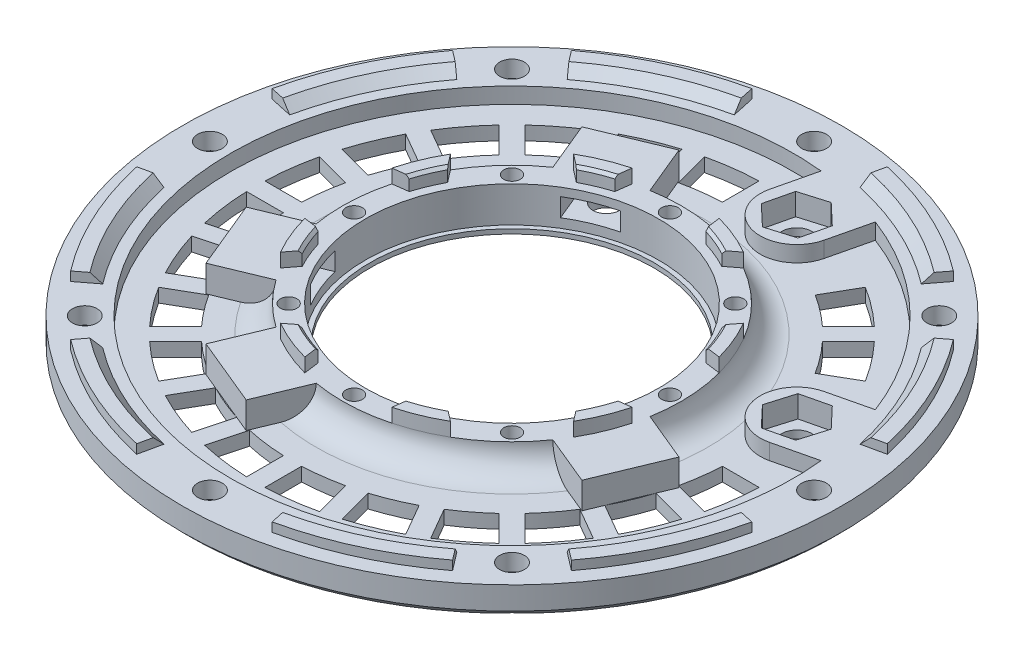
SolidWorks part; units mm, degrees
ref_plane "Front Plane" through (0, 0, 0) normal (0, 0, 1) x (1, 0, 0)
ref_plane "Top Plane" through (0, 0, 0) normal (0, 1, 0) x (1, 0, 0)
ref_plane "Right Plane" through (0, 0, 0) normal (1, 0, 0) x (0, 0, -1)
sketch "Sketch1" plane through (0, 0, 0) normal (0, 1, 0) x (1, 0, 0)
  circle A0 centre (0, 0) radius 16.025
  circle A1 centre (0, 0) radius 36
  dimension "D1" = 32.05
  dimension "D2" = 72
extrude "Boss-Extrude1" add sketch "Sketch1" along normal blind 1
sketch "Sketch2" plane through (0, 0, 0) normal (0, -1, 0) x (1, 0, 0)
  circle A0 centre (0, 0) radius 17.25 construction
  circle A1 centre (0, 0) radius 18.5 construction
  circle A2 centre (0, 0) radius 18.5
  circle A3 centre (0, 0) radius 16.025 construction
  circle A4 centre (0, 0) radius 16.025
  arc A5 (-1.2, 18.461) -> (-4.705, 17.8917) centre (0, 0) ccw construction
  point P3 (0, -17.25)
extrude "Boss-Extrude2" add sketch "Sketch2" against normal offset from surface (3.9 mm away) 3.9 up to face at (0, 0, 36)
fillet "Fillet1" radius 2.9 1 edges at (0, 1, 18.5)
sketch "Sketch4" plane through (0, 0, 0) normal (0, 1, 0) x (1, 0, 0)
  circle A0 centre (0, 0) radius 15.525
  circle A1 centre (0, 0) radius 36
  circle A2 centre (0, 0) radius 36
  circle A3 centre (0, 0) radius 16.025 construction
  dimension "D2" = 0.5
  dimension "D1" = 0
extrude "Boss-Extrude3" add sketch "Sketch4" against normal blind 0.5
sketch "Sketch5" plane through (0, 1, 0) normal (0, 1, 0) x (1, 0, 0)
  line L0 (27.99, -0.75) -> (19.9859, -0.75) construction
  line L1 (19.9859, 0.75) -> (27.99, 0.75) construction
  line L2 (27.99, -0.75) -> (19.9859, -0.75) construction
  line L3 (19.9859, 0.75) -> (27.99, 0.75) construction
  line L4 (0, 0) -> (36, 0) construction
  line L5 (0, 0) -> (34.7733, 9.3175) construction
  line L6 (34.7733, 9.3175) -> (36, 0) construction
  line L7 (0, 0) -> (35.3867, 4.6587) construction
  line L8 (27.99, 1) -> (23.9792, 1)
  line L9 (27.295, 6.2784) -> (23.4209, 5.2403)
  line L10 (27.99, -1) -> (23.9792, -1)
  line L11 (27.295, -6.2784) -> (23.4209, -5.2403)
  line L12 (26.7774, -8.2103) -> (22.9033, -7.1722)
  line L13 (24.74, -13.129) -> (21.2666, -11.1236)
  line L14 (23.74, -14.861) -> (20.2666, -12.8556)
  line L15 (20.499, -19.0848) -> (17.6629, -16.2487)
  line L16 (19.0848, -20.499) -> (16.2487, -17.6629)
  line L17 (14.861, -23.74) -> (12.8556, -20.2666)
  line L18 (13.129, -24.74) -> (11.1236, -21.2666)
  line L19 (8.2103, -26.7774) -> (7.1722, -22.9033)
  line L20 (6.2784, -27.295) -> (5.2403, -23.4209)
  line L21 (1, -27.99) -> (1, -23.9792)
  line L22 (-1, -27.99) -> (-1, -23.9792)
  line L23 (-6.2784, -27.295) -> (-5.2403, -23.4209)
  line L24 (-8.2103, -26.7774) -> (-7.1722, -22.9033)
  line L25 (-13.129, -24.74) -> (-11.1236, -21.2666)
  line L26 (-14.861, -23.74) -> (-12.8556, -20.2666)
  line L27 (-19.0848, -20.499) -> (-16.2487, -17.6629)
  line L28 (-20.499, -19.0848) -> (-17.6629, -16.2487)
  line L29 (-23.74, -14.861) -> (-20.2666, -12.8556)
  line L30 (-24.74, -13.129) -> (-21.2666, -11.1236)
  line L31 (-26.7774, -8.2103) -> (-22.9033, -7.1722)
  line L32 (-27.295, -6.2784) -> (-23.4209, -5.2403)
  line L33 (-27.99, -1) -> (-23.9792, -1)
  line L34 (-27.99, 1) -> (-23.9792, 1)
  line L35 (-27.295, 6.2784) -> (-23.4209, 5.2403)
  line L36 (-26.7774, 8.2103) -> (-22.9033, 7.1722)
  line L37 (-24.74, 13.129) -> (-21.2666, 11.1236)
  line L38 (-23.74, 14.861) -> (-20.2666, 12.8556)
  line L39 (-20.499, 19.0848) -> (-17.6629, 16.2487)
  line L40 (-19.0848, 20.499) -> (-16.2487, 17.6629)
  line L41 (-14.861, 23.74) -> (-12.8556, 20.2666)
  line L42 (-13.129, 24.74) -> (-11.1236, 21.2666)
  line L43 (-8.2103, 26.7774) -> (-7.1722, 22.9033)
  line L44 (-6.2784, 27.295) -> (-5.2403, 23.4209)
  line L45 (-1, 27.99) -> (-1, 23.9792)
  line L46 (1, 27.99) -> (1, 23.9792)
  line L47 (6.2784, 27.295) -> (5.2403, 23.4209)
  line L48 (8.2103, 26.7774) -> (7.1722, 22.9033)
  line L49 (13.129, 24.74) -> (11.1236, 21.2666)
  line L50 (14.861, 23.74) -> (12.8556, 20.2666)
  line L51 (19.0848, 20.499) -> (16.2487, 17.6629)
  line L52 (20.499, 19.0848) -> (17.6629, 16.2487)
  line L53 (23.74, 14.861) -> (20.2666, 12.8556)
  line L54 (24.74, 13.129) -> (21.2666, 11.1236)
  line L55 (26.7774, 8.2103) -> (22.9033, 7.1722)
  line L56 (0, 0) -> (23.9792, 1) construction
  circle A0 centre (0, 0) radius 24 construction
  circle A2 centre (0, 0) radius 36 construction
  arc A3 (23.9792, 1) -> (23.4209, 5.2403) centre (0, 0) ccw
  arc A4 (27.99, 1) -> (27.295, 6.2784) centre (0, 0) ccw
  arc A5 (27.295, -6.2784) -> (27.99, -1) centre (0, 0) ccw
  arc A6 (23.4209, -5.2403) -> (23.9792, -1) centre (0, 0) ccw
  arc A7 (24.74, -13.129) -> (26.7774, -8.2103) centre (0, 0) ccw
  arc A8 (21.2666, -11.1236) -> (22.9033, -7.1722) centre (0, 0) ccw
  arc A9 (20.499, -19.0848) -> (23.74, -14.861) centre (0, 0) ccw
  arc A10 (17.6629, -16.2487) -> (20.2666, -12.8556) centre (0, 0) ccw
  arc A11 (14.861, -23.74) -> (19.0848, -20.499) centre (0, 0) ccw
  arc A12 (12.8556, -20.2666) -> (16.2487, -17.6629) centre (0, 0) ccw
  arc A13 (8.2103, -26.7774) -> (13.129, -24.74) centre (0, 0) ccw
  arc A14 (7.1722, -22.9033) -> (11.1236, -21.2666) centre (0, 0) ccw
  arc A15 (1, -27.99) -> (6.2784, -27.295) centre (0, 0) ccw
  arc A16 (1, -23.9792) -> (5.2403, -23.4209) centre (0, 0) ccw
  arc A17 (-6.2784, -27.295) -> (-1, -27.99) centre (0, 0) ccw
  arc A18 (-5.2403, -23.4209) -> (-1, -23.9792) centre (0, 0) ccw
  arc A19 (-13.129, -24.74) -> (-8.2103, -26.7774) centre (0, 0) ccw
  arc A20 (-11.1236, -21.2666) -> (-7.1722, -22.9033) centre (0, 0) ccw
  arc A21 (-19.0848, -20.499) -> (-14.861, -23.74) centre (0, 0) ccw
  arc A22 (-16.2487, -17.6629) -> (-12.8556, -20.2666) centre (0, 0) ccw
  arc A23 (-23.74, -14.861) -> (-20.499, -19.0848) centre (0, 0) ccw
  arc A24 (-20.2666, -12.8556) -> (-17.6629, -16.2487) centre (0, 0) ccw
  arc A25 (-26.7774, -8.2103) -> (-24.74, -13.129) centre (0, 0) ccw
  arc A26 (-22.9033, -7.1722) -> (-21.2666, -11.1236) centre (0, 0) ccw
  arc A27 (-27.99, -1) -> (-27.295, -6.2784) centre (0, 0) ccw
  arc A28 (-23.9792, -1) -> (-23.4209, -5.2403) centre (0, 0) ccw
  arc A29 (-27.295, 6.2784) -> (-27.99, 1) centre (0, 0) ccw
  arc A30 (-23.4209, 5.2403) -> (-23.9792, 1) centre (0, 0) ccw
  arc A31 (-24.74, 13.129) -> (-26.7774, 8.2103) centre (0, 0) ccw
  arc A32 (-21.2666, 11.1236) -> (-22.9033, 7.1722) centre (0, 0) ccw
  arc A33 (-20.499, 19.0848) -> (-23.74, 14.861) centre (0, 0) ccw
  arc A34 (-17.6629, 16.2487) -> (-20.2666, 12.8556) centre (0, 0) ccw
  arc A35 (-14.861, 23.74) -> (-19.0848, 20.499) centre (0, 0) ccw
  arc A36 (-12.8556, 20.2666) -> (-16.2487, 17.6629) centre (0, 0) ccw
  arc A37 (-8.2103, 26.7774) -> (-13.129, 24.74) centre (0, 0) ccw
  arc A38 (-7.1722, 22.9033) -> (-11.1236, 21.2666) centre (0, 0) ccw
  arc A39 (-1, 27.99) -> (-6.2784, 27.295) centre (0, 0) ccw
  arc A40 (-1, 23.9792) -> (-5.2403, 23.4209) centre (0, 0) ccw
  arc A41 (6.2784, 27.295) -> (1, 27.99) centre (0, 0) ccw
  arc A42 (5.2403, 23.4209) -> (1, 23.9792) centre (0, 0) ccw
  arc A43 (13.129, 24.74) -> (8.2103, 26.7774) centre (0, 0) ccw
  arc A44 (11.1236, 21.2666) -> (7.1722, 22.9033) centre (0, 0) ccw
  arc A45 (19.0848, 20.499) -> (14.861, 23.74) centre (0, 0) ccw
  arc A46 (16.2487, 17.6629) -> (12.8556, 20.2666) centre (0, 0) ccw
  arc A47 (23.74, 14.861) -> (20.499, 19.0848) centre (0, 0) ccw
  arc A48 (20.2666, 12.8556) -> (17.6629, 16.2487) centre (0, 0) ccw
  arc A49 (26.7774, 8.2103) -> (24.74, 13.129) centre (0, 0) ccw
  arc A50 (22.9033, 7.1722) -> (21.2666, 11.1236) centre (0, 0) ccw
  dimension "D1" = 15
  dimension "D2" = 1
  dimension "D4" = 24
  dimension "D3" = 24
extrude "Cut-Extrude1" cut sketch "Sketch5" against normal through all both and the other way through all
sketch "Sketch7" plane through (0, 3.9, 0) normal (0, 1, 0) x (1, 0, 0)
  line L0 (0, 0) -> (0, 17.25) construction
  circle A0 centre (0, 17.25) radius 0.9
  circle A1 centre (12.1976, 12.1976) radius 0.9
  circle A2 centre (17.25, 0) radius 0.9
  circle A3 centre (12.1976, -12.1976) radius 0.9
  circle A4 centre (0, -17.25) radius 0.9
  circle A5 centre (-12.1976, -12.1976) radius 0.9
  circle A6 centre (-17.25, 0) radius 0.9
  circle A7 centre (-12.1976, 12.1976) radius 0.9
  point P21 (0, 0)
  dimension "D1" = 1.8
  dimension "D2" = 8
extrude "Cut-Extrude2" cut sketch "Sketch7" against normal through all
sketch "Sketch8" plane through (0, 1, 0) normal (0, 1, 0) x (1, 0, 0)
  arc A0 (-30.7407, -0.7544) -> (-30.0499, -6.5245) centre (0, 0) ccw construction
  arc A1 (-30.7407, -0.7544) -> (-30.0499, -6.5245) centre (0, 0) ccw construction
  arc A2 (-30.0499, 6.5245) -> (-30.7407, 0.7544) centre (0, 0) ccw construction
  arc A3 (-30.0499, 6.5245) -> (-30.7407, 0.7544) centre (0, 0) ccw construction
  circle A5 centre (0, 0) radius 30.75
  circle A6 centre (0, 0) radius 36 construction
  circle A7 centre (0, 0) radius 36
extrude "Boss-Extrude4" add sketch "Sketch8" along normal blind 1.7378
sketch "Sketch9" plane through (0, 2.7378, 0) normal (0, 1, 0) x (1, 0, 0)
  line L0 (0, 0) -> (-30.0499, 6.5245) construction
  line L1 (0, 0) -> (-30.0499, -6.5245) construction
  line L2 (-30.0499, 6.5245) -> (-30.0499, -6.5245) construction
  line L3 (-27.3707, 21.0023) -> (-23.9989, 18.415) construction
  line L4 (0, 0) -> (0, 36) construction
  line L5 (0, 0) -> (-25.4558, 25.4558) construction
  line L6 (-24.3956, 18.7194) -> (0, 0) construction
  line L7 (-24.3956, 18.7194) -> (-28.5607, 21.9154) construction
  line L8 (-30.0499, 6.5245) -> (-35.1803, 7.6384) construction
  line L9 (-27.3521, 20.862) -> (-25.3687, 19.3401)
  line L10 (-31.2086, 14.47) -> (0, 0) construction
  line L11 (-33.5954, 7.3966) -> (-31.1523, 6.8662)
  line L12 (-7.3966, 33.5954) -> (-6.8662, 31.1523)
  line L13 (-20.862, 27.3521) -> (-19.3401, 25.3687)
  arc A0 (-30.0499, 6.5245) -> (-24.3956, 18.7194) centre (0, 0) cw construction
  arc A1 (-35.1803, 7.6384) -> (-28.5607, 21.9154) centre (0, 0) cw construction
  circle A2 centre (0, 0) radius 36 construction
  circle A3 centre (0, 0) radius 30.75 construction
  arc A4 (-27.2914, 20.9414) -> (-33.6168, 7.2989) centre (0, 0) ccw construction
  arc A5 (-31.1523, 6.8662) -> (-25.3687, 19.3401) centre (0, 0) cw
  arc A6 (-33.5954, 7.3966) -> (-27.3521, 20.862) centre (0, 0) cw
  circle A7 centre (0, 0) radius 36 construction
  arc A8 (-6.8662, 31.1523) -> (-19.3401, 25.3687) centre (0, 0) ccw
  arc A9 (-7.3966, 33.5954) -> (-20.862, 27.3521) centre (0, 0) ccw
  dimension "D2" = 0.1
  dimension "D3" = 45
  dimension "D4" = 0.1
  dimension "D1" = 2.5
extrude "Boss-Extrude5" add sketch "Sketch9" along normal blind 1
ref_axis "Axis1" through (0, -0.72, 0) along (0, 1, 0)
pattern_circular "CirPattern1" count 4 over 360 about axis through (0, -0.72, 0) along (0, 1, 0) of "Boss-Extrude5"
chamfer "Chamfer1" distance 1 angle 45 8 edges at (-28.9406, 3.7378, -13.4184) (-13.4184, 3.7378, -28.9406) (13.4184, 3.7378, -28.9406) (28.9406, 3.7378, -13.4184) (28.9406, 3.7378, 13.4184) (13.4184, 3.7378, 28.9406) (-13.4184, 3.7378, 28.9406) (-28.9406, 3.7378, 13.4184)
sketch "Sketch10" plane through (0, 2.7378, 0) normal (0, 1, 0) x (1, 0, 0)
  line L0 (0, 0) -> (0, 36) construction
  circle A0 centre (0, 0) radius 36 construction
  circle A1 centre (0, 33) radius 1.1 construction
  circle A2 centre (0, 33) radius 1.1
  circle A3 centre (23.3345, 23.3345) radius 1.1
  circle A4 centre (33, 0) radius 1.1
  circle A5 centre (23.3345, -23.3345) radius 1.1
  circle A6 centre (0, -33) radius 1.1
  circle A7 centre (-23.3345, -23.3345) radius 1.1
  circle A8 centre (-33, 0) radius 1.1
  circle A9 centre (-23.3345, 23.3345) radius 1.1
  point P26 (0, 0)
  dimension "D1" = 8
extrude "Cut-Extrude3" cut sketch "Sketch10" against normal through all both and the other way through all
chamfer "Chamfer2" distance 0.75 angle 45 1 edges at (0, -0.5, 36)
hole_wizard "CSK for M2.5 Flat Head Machine Screw1" positions "Sketch11" profile "Sketch12" countersink size "M2.5" standard "ANSI Metric" end condition through all
sketch "Sketch11" plane through (0, -0.5, 0) normal (0, -1, 0) x (-1, 0, 0)
  point P0 (0, -33)
  point P3 (23.3345, -23.3345)
  point P6 (33, 0)
  point P9 (23.3345, 23.3345)
  point P12 (0, 33)
  point P15 (-23.3345, 23.3345)
  point P18 (-33, 0)
  point P21 (-23.3345, -23.3345)
sketch "Sketch12" plane through (0, -0.5, 33) normal (1, 0, 0) x (0, 0, -1)
  line L0 (0, 0) -> (0, 4.4)
  line L1 (0, 4.4) -> (1.35, 4.4)
  line L2 (1.35, 4.4) -> (1.35, 1.4)
  line L3 (1.35, 1.4) -> (2.75, 0)
  line L5 (2.75, 0) -> (0, 0)
  line L6 (-1.35, 1.4) -> (-2.75, 0) construction
  line L11 (0, -6.35) -> (0, 107.95) construction
  dimension "Thru Hole Dia." = 2.7
  dimension "Thru Hole Depth" = 4.4
  dimension "Near C'Sink Dia." = 5.5
  dimension "Near C'Sink Angle" = 90
sketch "Sketch13" plane through (0, 3.9, 0) normal (0, 1, 0) x (1, 0, 0)
  line L0 (0, 0) -> (-7.0796, 17.0918) construction
  line L1 (0, 0) -> (0, 18.5) construction
  line L2 (-9.2808, 16.0037) -> (-7.9403, 14.9751)
  line L3 (-4.7538, 17.8788) -> (-4.9743, 16.2037)
  line L4 (4.7538, 17.8788) -> (4.9743, 16.2037)
  line L5 (9.2808, 16.0037) -> (7.9403, 14.9751)
  line L6 (16.0037, 9.2808) -> (14.9751, 7.9403)
  line L7 (17.8788, 4.7538) -> (16.2037, 4.9743)
  line L8 (17.8788, -4.7538) -> (16.2037, -4.9743)
  line L9 (16.0037, -9.2808) -> (14.9751, -7.9403)
  line L10 (9.2808, -16.0037) -> (7.9403, -14.9751)
  line L11 (4.7538, -17.8788) -> (4.9743, -16.2037)
  line L12 (-4.7538, -17.8788) -> (-4.9743, -16.2037)
  line L13 (-9.2808, -16.0037) -> (-7.9403, -14.9751)
  line L14 (-16.0037, -9.2808) -> (-14.9751, -7.9403)
  line L15 (-17.8788, -4.7538) -> (-16.2037, -4.9743)
  line L16 (-17.8788, 4.7538) -> (-16.2037, 4.9743)
  line L17 (-16.0037, 9.2808) -> (-14.9751, 7.9403)
  circle A0 centre (0, 0) radius 18.5 construction
  arc A1 (-7.9403, 14.9751) -> (-4.9743, 16.2037) centre (0, 0) cw
  arc A2 (-9.2808, 16.0037) -> (-4.7538, 17.8788) centre (0, 0) cw
  arc A3 (4.9743, 16.2037) -> (7.9403, 14.9751) centre (0, 0) cw
  arc A4 (4.7538, 17.8788) -> (9.2808, 16.0037) centre (0, 0) cw
  arc A5 (14.9751, 7.9403) -> (16.2037, 4.9743) centre (0, 0) cw
  arc A6 (16.0037, 9.2808) -> (17.8788, 4.7538) centre (0, 0) cw
  arc A7 (16.2037, -4.9743) -> (14.9751, -7.9403) centre (0, 0) cw
  arc A8 (17.8788, -4.7538) -> (16.0037, -9.2808) centre (0, 0) cw
  arc A9 (7.9403, -14.9751) -> (4.9743, -16.2037) centre (0, 0) cw
  arc A10 (9.2808, -16.0037) -> (4.7538, -17.8788) centre (0, 0) cw
  arc A11 (-4.9743, -16.2037) -> (-7.9403, -14.9751) centre (0, 0) cw
  arc A12 (-4.7538, -17.8788) -> (-9.2808, -16.0037) centre (0, 0) cw
  arc A13 (-14.9751, -7.9403) -> (-16.2037, -4.9743) centre (0, 0) cw
  arc A14 (-16.0037, -9.2808) -> (-17.8788, -4.7538) centre (0, 0) cw
  arc A15 (-16.2037, 4.9743) -> (-14.9751, 7.9403) centre (0, 0) cw
  arc A16 (-17.8788, 4.7538) -> (-16.0037, 9.2808) centre (0, 0) cw
  point P12 (-6.4865, 15.6598)
  point P20 (6.4865, 15.6598)
  point P25 (15.6598, 6.4865)
  point P30 (15.6598, -6.4865)
  point P35 (6.4865, -15.6598)
  point P40 (-6.4865, -15.6598)
  point P45 (-15.6598, -6.4865)
  point P50 (-15.6598, 6.4865)
  point P51 (0, 0)
  dimension "D1" = 22.5
  dimension "D2" = 30
  dimension "D3" = 1.55
  dimension "D4" = 4.9
  dimension "D5" = 8
extrude "Boss-Extrude6" add sketch "Sketch13" along normal blind 1.5
chamfer "Chamfer3" distance 0.3 angle 45 8 edges at (-15.6598, 5.4, -6.4865) (-15.6598, 5.4, 6.4865) (-6.4865, 5.4, 15.6598) (6.4865, 5.4, 15.6598) (15.6598, 5.4, 6.4865) (15.6598, 5.4, -6.4865) (6.4865, 5.4, -15.6598) (-6.4865, 5.4, -15.6598)
sketch "Sketch14" plane through (0, -0.5, 0) normal (0, -1, 0) x (1, 0, 0)
  line L0 (0, 0) -> (25.4558, -25.4558) construction
  line L1 (0, 0) -> (0, -36) construction
  line L6 (0, 0) -> (-22.1731, 9.1844) construction
  line L7 (0, 0) -> (-9.1844, -22.1731) construction
  circle A0 centre (0, 0) radius 36 construction
  circle A1 centre (0, 0) radius 16.025 construction
  arc A5 (-21.2666, 11.1236) -> (-22.9033, 7.1722) centre (0, 0) ccw construction
  circle A6 centre (-17.5768, 7.2806) radius 1.45
  circle A7 centre (-17.5768, 7.2806) radius 4.975 construction
  arc A8 (-11.1236, -21.2666) -> (-7.1722, -22.9033) centre (0, 0) ccw construction
  circle A9 centre (-7.2806, -17.5768) radius 1.45
  circle A10 centre (-7.2806, -17.5768) radius 4.975 construction
  circle A11 centre (17.5768, 7.2806) radius 1.45
  circle A12 centre (-7.2806, 17.5768) radius 1.45
  point P25 (-14.8052, 6.1325)
  point P28 (-16.2372, 6.7257)
  dimension "D2" = 2.9
  dimension "D3" = 3
  dimension "D1" = 45
sketch "Sketch15" plane through (0, 1, 0) normal (0, 1, 0) x (1, 0, 0)
  line L0 (-9.8825, 13.2519) -> (-12.8979, 20.5316)
  line L1 (-9.8825, 13.2519) -> (-2.3825, 16.3585)
  line L2 (-12.8979, 20.5316) -> (-5.3979, 23.6382)
  line L3 (-2.3825, 16.3585) -> (-5.3979, 23.6382)
  line L4 (-9.8825, 13.2519) -> (-5.3979, 23.6382) construction
  line L5 (-12.8979, 20.5316) -> (-2.3825, 16.3585) construction
  line L6 (0, 0) -> (-9.1844, 22.1731) construction
  line L7 (2.3825, 16.3585) -> (5.3979, 23.6382) [skipped]
  line L8 (2.3825, 16.3585) -> (9.8825, 13.2519) [skipped]
  line L9 (5.3979, 23.6382) -> (12.8979, 20.5316) [skipped]
  line L10 (9.8825, 13.2519) -> (12.8979, 20.5316) [skipped]
  line L11 (2.3825, 16.3585) -> (12.8979, 20.5316) construction
  line L12 (5.3979, 23.6382) -> (9.8825, 13.2519) construction
  line L13 (13.2519, 9.8825) -> (20.5316, 12.8979) [skipped]
  line L14 (13.2519, 9.8825) -> (16.3585, 2.3825) [skipped]
  line L15 (20.5316, 12.8979) -> (23.6382, 5.3979) [skipped]
  line L16 (16.3585, 2.3825) -> (23.6382, 5.3979) [skipped]
  line L17 (13.2519, 9.8825) -> (23.6382, 5.3979) construction
  line L18 (20.5316, 12.8979) -> (16.3585, 2.3825) construction
  line L19 (16.3585, -2.3825) -> (23.6382, -5.3979)
  line L20 (16.3585, -2.3825) -> (13.2519, -9.8825)
  line L21 (23.6382, -5.3979) -> (20.5316, -12.8979)
  line L22 (13.2519, -9.8825) -> (20.5316, -12.8979)
  line L23 (16.3585, -2.3825) -> (20.5316, -12.8979) construction
  line L24 (23.6382, -5.3979) -> (13.2519, -9.8825) construction
  line L25 (9.8825, -13.2519) -> (12.8979, -20.5316) [skipped]
  line L26 (9.8825, -13.2519) -> (2.3825, -16.3585) [skipped]
  line L27 (12.8979, -20.5316) -> (5.3979, -23.6382) [skipped]
  line L28 (2.3825, -16.3585) -> (5.3979, -23.6382) [skipped]
  line L29 (9.8825, -13.2519) -> (5.3979, -23.6382) construction
  line L30 (12.8979, -20.5316) -> (2.3825, -16.3585) construction
  line L31 (-2.3825, -16.3585) -> (-5.3979, -23.6382)
  line L32 (-2.3825, -16.3585) -> (-9.8825, -13.2519)
  line L33 (-5.3979, -23.6382) -> (-12.8979, -20.5316)
  line L34 (-9.8825, -13.2519) -> (-12.8979, -20.5316)
  line L35 (-2.3825, -16.3585) -> (-12.8979, -20.5316) construction
  line L36 (-5.3979, -23.6382) -> (-9.8825, -13.2519) construction
  line L37 (-13.2519, -9.8825) -> (-20.5316, -12.8979)
  line L38 (-13.2519, -9.8825) -> (-16.3585, -2.3825)
  line L39 (-20.5316, -12.8979) -> (-23.6382, -5.3979)
  line L40 (-16.3585, -2.3825) -> (-23.6382, -5.3979)
  line L41 (-13.2519, -9.8825) -> (-23.6382, -5.3979) construction
  line L42 (-20.5316, -12.8979) -> (-16.3585, -2.3825) construction
  line L43 (-16.3585, 2.3825) -> (-23.6382, 5.3979) [skipped]
  line L44 (-16.3585, 2.3825) -> (-13.2519, 9.8825) [skipped]
  line L45 (-23.6382, 5.3979) -> (-20.5316, 12.8979) [skipped]
  line L46 (-13.2519, 9.8825) -> (-20.5316, 12.8979) [skipped]
  line L47 (-16.3585, 2.3825) -> (-20.5316, 12.8979) construction
  line L48 (-23.6382, 5.3979) -> (-13.2519, 9.8825) construction
  line L49 (0, 0) -> (-9.1844, 22.1731) construction
  arc A1 (-7.1722, 22.9033) -> (-11.1236, 21.2666) centre (0, 0) ccw construction
  circle A2 centre (0, 0) radius 16.025 construction
  point P1 (-7.6402, 18.445)
  point P9 (7.6402, 18.445)
  point P18 (18.445, 7.6402)
  point P23 (18.445, -7.6402)
  point P28 (7.6402, -18.445)
  point P33 (-7.6402, -18.445)
  point P38 (-18.445, -7.6402)
  point P43 (-18.445, 7.6402)
  point P48 (0, 0)
  dimension "D1" = 7.5
  dimension "D2" = 8
extrude "Boss-Extrude7" add sketch "Sketch15" along normal up to surface (2.9 mm away) up to face at (0, 3.9, -16.35)
extrude "Cut-Extrude4" cut sketch "Sketch14" against normal blind 3.5
sketch "Sketch16" plane through (0, -0.5, 0) normal (0, -1, 0) x (1, 0, 0)
  line L0 (0, 0) -> (23.3345, -23.3345) construction
  line L1 (10.1026, 7.7782) -> (22.348, -8.1266) construction
  line L2 (0, 0) -> (0, -17.25) construction
  line L3 (0, 0) -> (10.1026, 7.7782) construction
  line L4 (18.6021, 8.3059) -> (13.454, 13.454) construction
  line L5 (0, 0) -> (13.454, 13.454) construction
  line L6 (25.1212, -5.9915) -> (27.5961, -3.5166) construction
  line L7 (27.5961, -3.5166) -> (12.0398, 12.0398) construction
  circle A0 centre (0, 0) radius 12.75 construction
  circle A1 centre (25.1212, -5.9915) radius 1.65
  circle A2 centre (25.1212, -5.9915) radius 3.5 construction
  circle A3 centre (17.5768, 7.2806) radius 1.45 construction
  circle A4 centre (5.9915, -25.1212) radius 1.65
  dimension "D1" = 25.5
  dimension "D2" = 3.3
  dimension "D3" = 7
  dimension "D4" = 2
  dimension "D5" = 22
sketch "Sketch17" plane through (0, -0.5, 0) normal (0, -1, 0) x (1, 0, 0)
  line L0 (24.74, -13.129) -> (21.2666, -11.1236) construction
  line L1 (24.74, -13.129) -> (21.2666, -11.1236)
  line L2 (0, 0) -> (12.1976, -12.1976) construction
  line L3 (13.129, -24.74) -> (11.1236, -21.2666)
  arc A0 (21.2666, -11.1236) -> (22.9033, -7.1722) centre (0, 0) ccw construction
  arc A1 (24.74, -13.129) -> (26.7774, -8.2103) centre (0, 0) ccw construction
  arc A4 (21.2666, -11.1236) -> (21.5701, -10.5228) centre (0, 0) ccw
  arc A5 (24.74, -13.129) -> (25.4284, -11.7403) centre (0, 0) ccw
  arc A8 (25.4284, -11.7403) -> (21.5701, -10.5228) centre (25.1212, -5.9915) ccw
  arc A9 (11.7403, -25.4284) -> (10.5228, -21.5701) centre (5.9915, -25.1212) cw
  arc A10 (13.129, -24.74) -> (11.7403, -25.4284) centre (0, 0) cw
  arc A11 (11.1236, -21.2666) -> (10.5228, -21.5701) centre (0, 0) cw
extrude "Boss-Extrude8" add sketch "Sketch17" against normal up to surface (1.5 mm away) up to face at (25.7264, 1, -3.3869)
sketch "Sketch18" plane through (0, 1, 0) normal (0, 1, 0) x (1, 0, 0)
  line L0 (0, 0) -> (25.1212, 5.9915) construction
  line L1 (24.1933, 9.8823) -> (28.7289, 10.9641)
  line L2 (26.0492, 2.1006) -> (30.5849, 3.1823)
  line L3 (0, 0) -> (23.3345, 23.3345) construction
  line L4 (9.8823, 24.1933) -> (10.9641, 28.7289)
  line L5 (2.1006, 26.0492) -> (3.1823, 30.5849)
  arc A0 (24.1933, 9.8823) -> (26.0492, 2.1006) centre (25.1212, 5.9915) ccw
  circle A1 centre (0, 0) radius 30.75 construction
  circle A2 centre (0, 0) radius 30.75 construction
  arc A3 (30.5849, 3.1823) -> (28.7289, 10.9641) centre (0, 0) ccw
  arc A4 (3.1823, 30.5849) -> (10.9641, 28.7289) centre (0, 0) cw
  arc A5 (9.8823, 24.1933) -> (2.1006, 26.0492) centre (5.9915, 25.1212) cw
  circle A6 centre (23.3345, 23.3345) radius 1.1 construction
  point P11 (0, 0)
  point P19 (0, 0)
  dimension "D1" = 8
extrude "Boss-Extrude9" add sketch "Sketch18" along normal up to surface (1.7378 mm away) up to face at (0, 2.7378, 34.35)
extrude "Cut-Extrude5" cut sketch "Sketch16" against normal through all
sketch "Sketch19" plane through (0, 2.7378, 0) normal (0, 1, 0) x (1, 0, 0)
  line L0 (0, 0) -> (25.1212, 5.9915) construction
  line L1 (28.1539, 6.7147) -> (26.0112, 8.9794)
  line L2 (26.0112, 8.9794) -> (22.9785, 8.2561)
  line L3 (22.9785, 8.2561) -> (22.0886, 5.2682)
  line L4 (22.0886, 5.2682) -> (24.2313, 3.0035)
  line L5 (24.2313, 3.0035) -> (27.2639, 3.7268)
  line L6 (27.2639, 3.7268) -> (28.1539, 6.7147)
  line L7 (0, 0) -> (23.3345, 23.3345) construction
  line L8 (3.7268, 27.2639) -> (6.7147, 28.1539)
  line L9 (3.0035, 24.2313) -> (3.7268, 27.2639)
  line L10 (5.2682, 22.0886) -> (3.0035, 24.2313)
  line L11 (8.2561, 22.9785) -> (5.2682, 22.0886)
  line L12 (8.9794, 26.0112) -> (8.2561, 22.9785)
  line L13 (6.7147, 28.1539) -> (8.9794, 26.0112)
  circle A0 centre (25.1212, 5.9915) radius 2.7 construction
  circle A1 centre (23.3345, 23.3345) radius 1.35 construction
  point P19 (0, 0)
  point P20 (0, 0)
  dimension "D1" = 5.4
extrude "Cut-Extrude6" cut sketch "Sketch19" against normal blind 2.4
sketch "Sketch20" plane through (0, 3, 0) normal (0, -1, 0) x (1, 0, 0)
  line L0 (0, 0) -> (-17.5768, 7.2806) construction
  line L5 (-15.2866, 9.0379) -> (-13.6672, 8.3671)
  line L6 (-14.9098, 6.1758) -> (-15.2866, 9.0379) construction
  line L16 (-15.2866, 9.0379) -> (-17.9536, 10.1426)
  line L17 (-17.9536, 10.1426) -> (-20.2438, 8.3853)
  line L18 (-20.2438, 8.3853) -> (-19.867, 5.5232)
  line L19 (-19.867, 5.5232) -> (-17.2, 4.4185)
  line L20 (-17.2, 4.4185) -> (-14.9098, 6.1758) construction
  line L21 (-13.6672, 8.3671) -> (-15.5806, 3.7477)
  line L28 (-15.5806, 3.7477) -> (-17.2, 4.4185)
  line L29 (-8.3671, 13.6672) -> (-9.0379, 15.2866)
  line L30 (-10.1426, 17.9536) -> (-9.0379, 15.2866)
  line L31 (-8.3853, 20.2438) -> (-10.1426, 17.9536)
  line L32 (-5.5232, 19.867) -> (-8.3853, 20.2438)
  line L33 (-4.4185, 17.2) -> (-5.5232, 19.867)
  line L34 (-4.4185, 17.2) -> (-3.7477, 15.5806)
  line L35 (-3.7477, 15.5806) -> (-8.3671, 13.6672)
  line L36 (3.7477, 15.5806) -> (4.4185, 17.2) [skipped]
  line L37 (5.5232, 19.867) -> (4.4185, 17.2) [skipped]
  line L38 (8.3853, 20.2438) -> (5.5232, 19.867) [skipped]
  line L39 (10.1426, 17.9536) -> (8.3853, 20.2438) [skipped]
  line L46 (9.0379, 15.2866) -> (10.1426, 17.9536) [skipped]
  line L47 (9.0379, 15.2866) -> (8.3671, 13.6672) [skipped]
  line L48 (8.3671, 13.6672) -> (3.7477, 15.5806) [skipped]
  line L49 (13.6672, 8.3671) -> (15.2866, 9.0379)
  line L50 (17.9536, 10.1426) -> (15.2866, 9.0379)
  line L51 (20.2438, 8.3853) -> (17.9536, 10.1426)
  line L52 (19.867, 5.5232) -> (20.2438, 8.3853)
  line L53 (17.2, 4.4185) -> (19.867, 5.5232)
  line L54 (17.2, 4.4185) -> (15.5806, 3.7477)
  line L55 (15.5806, 3.7477) -> (13.6672, 8.3671)
  line L56 (15.5806, -3.7477) -> (17.2, -4.4185) [skipped]
  line L57 (19.867, -5.5232) -> (17.2, -4.4185) [skipped]
  line L58 (20.2438, -8.3853) -> (19.867, -5.5232) [skipped]
  line L59 (17.9536, -10.1426) -> (20.2438, -8.3853) [skipped]
  line L60 (15.2866, -9.0379) -> (17.9536, -10.1426) [skipped]
  line L61 (15.2866, -9.0379) -> (13.6672, -8.3671) [skipped]
  line L62 (13.6672, -8.3671) -> (15.5806, -3.7477) [skipped]
  line L63 (8.3671, -13.6672) -> (9.0379, -15.2866) [skipped]
  line L64 (10.1426, -17.9536) -> (9.0379, -15.2866) [skipped]
  line L65 (8.3853, -20.2438) -> (10.1426, -17.9536) [skipped]
  line L66 (5.5232, -19.867) -> (8.3853, -20.2438) [skipped]
  line L67 (4.4185, -17.2) -> (5.5232, -19.867) [skipped]
  line L68 (4.4185, -17.2) -> (3.7477, -15.5806) [skipped]
  line L69 (3.7477, -15.5806) -> (8.3671, -13.6672) [skipped]
  line L70 (-3.7477, -15.5806) -> (-4.4185, -17.2)
  line L71 (-5.5232, -19.867) -> (-4.4185, -17.2)
  line L72 (-8.3853, -20.2438) -> (-5.5232, -19.867)
  line L73 (-10.1426, -17.9536) -> (-8.3853, -20.2438)
  line L74 (-9.0379, -15.2866) -> (-10.1426, -17.9536)
  line L75 (-9.0379, -15.2866) -> (-8.3671, -13.6672)
  line L76 (-8.3671, -13.6672) -> (-3.7477, -15.5806)
  line L77 (-13.6672, -8.3671) -> (-15.2866, -9.0379) [skipped]
  line L78 (-17.9536, -10.1426) -> (-15.2866, -9.0379) [skipped]
  line L79 (-20.2438, -8.3853) -> (-17.9536, -10.1426) [skipped]
  line L80 (-19.867, -5.5232) -> (-20.2438, -8.3853) [skipped]
  line L81 (-17.2, -4.4185) -> (-19.867, -5.5232) [skipped]
  line L82 (-17.2, -4.4185) -> (-15.5806, -3.7477) [skipped]
  line L83 (-15.5806, -3.7477) -> (-13.6672, -8.3671) [skipped]
  circle A1 centre (-17.5768, 7.2806) radius 2.5 construction
  circle A3 centre (0, 0) radius 16.025 construction
  point P57 (0, 0)
  point P69 (0, 0)
  dimension "D1" = 5
extrude "Cut-Extrude7" cut sketch "Sketch20" along normal blind 2
ref_plane "Plane1" through (0.6364, 0, 0.6364) normal (-0.7071, 0, -0.7071) x (-0.7071, 0, 0.7071)
